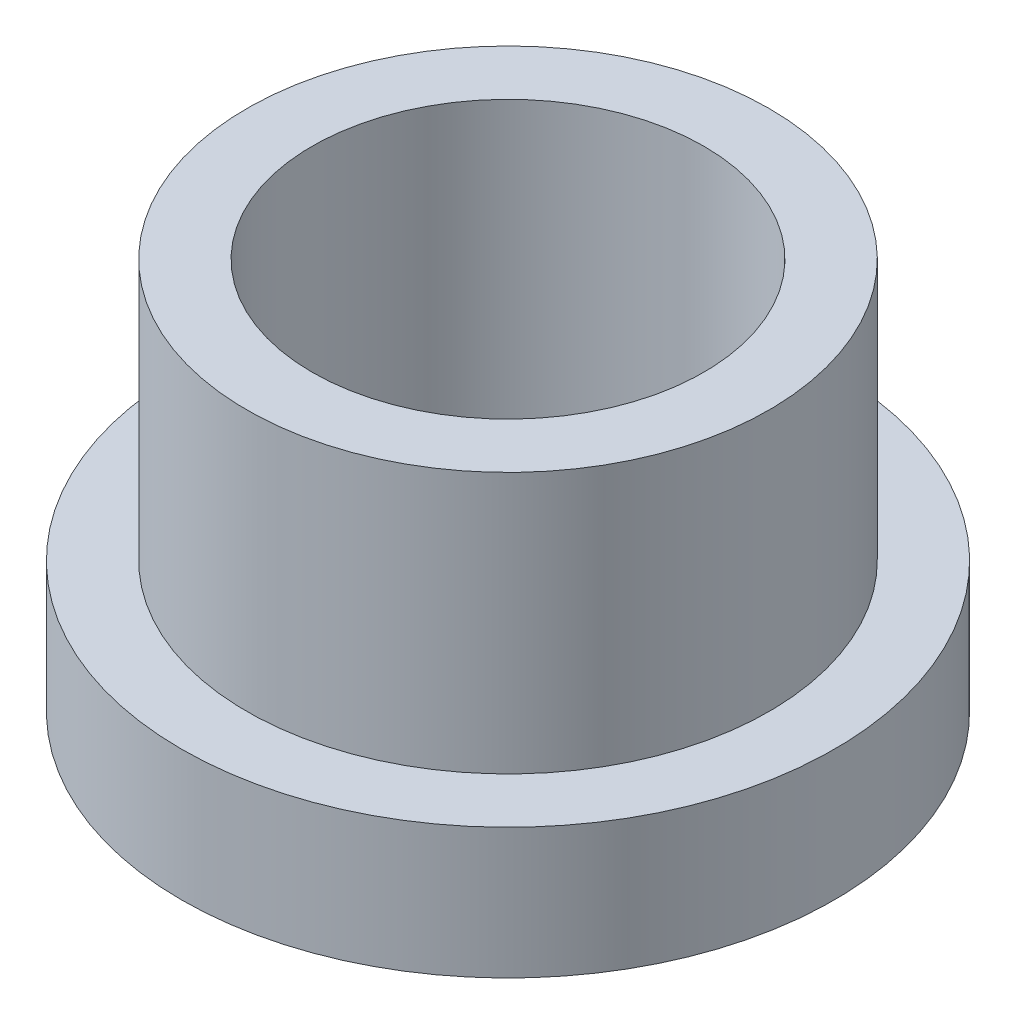
SolidWorks part; units mm, degrees
ref_plane "Front Plane" through (0, 0, 0) normal (0, 0, 1) x (1, 0, 0)
ref_plane "Top Plane" through (0, 0, 0) normal (0, 1, 0) x (1, 0, 0)
ref_plane "Right Plane" through (0, 0, 0) normal (1, 0, 0) x (0, 0, -1)
sketch "Sketch2" plane through (0, 0, 0) normal (0, 1, 0) x (1, 0, 0)
  circle A0 centre (0, 0) radius 7.9375
  dimension "D1" = 15.875
extrude "Boss-Extrude1" add sketch "Sketch2" along normal blind 3.175
sketch "Sketch3" plane through (0, 3.175, 0) normal (0, 1, 0) x (1, 0, 0)
  circle A0 centre (0, 0) radius 6.35
  dimension "D1" = 12.7
extrude "Boss-Extrude2" add sketch "Sketch3" along normal offset from surface (6.35 mm away) 9.525 contours A0 up to face at (0, 0, 7.9375)
sketch "Sketch4" plane through (0, 9.525, 0) normal (0, 1, 0) x (1, 0, 0)
  circle A0 centre (0, 0) radius 4.7625
  dimension "D1" = 9.525
extrude "Cut-Extrude1" cut sketch "Sketch4" against normal through all
